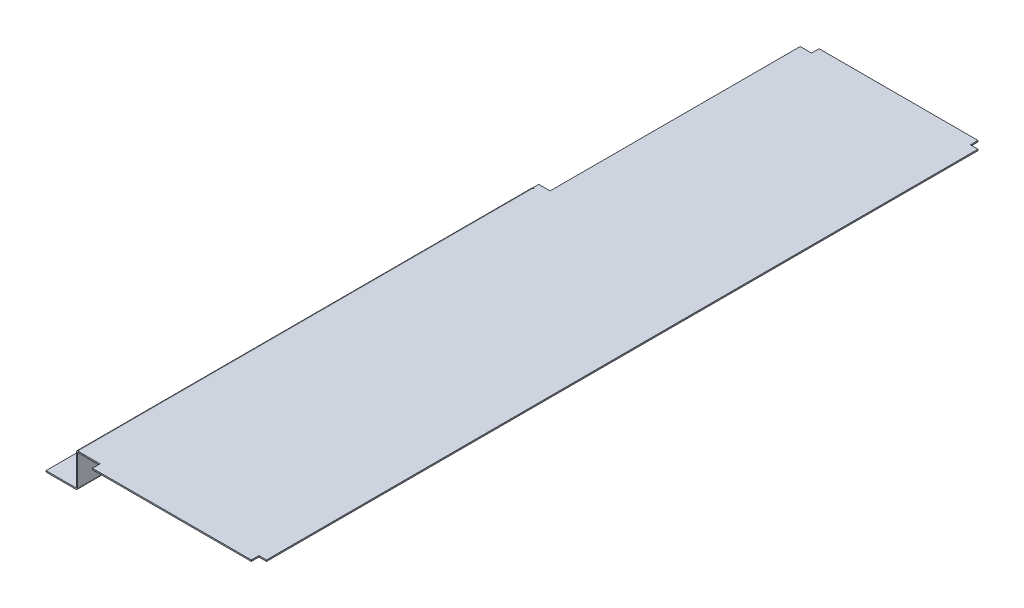
SolidWorks part; units mm, degrees
note: The reader was unsure of these and kept them because the rebuilt part matched: flange length of "Edge-Flange1", "Edge-Flange2".
ref_plane "Front Plane" through (0, 0, 0) normal (0, 0, 1) x (1, 0, 0)
ref_plane "Top Plane" through (0, 0, 0) normal (0, 1, 0) x (1, 0, 0)
ref_plane "Right Plane" through (0, 0, 0) normal (1, 0, 0) x (0, 0, -1)
sketch "Sketch1" plane through (0, 0, 0) normal (0, 1, 0) x (1, 0, 0)
  line L0 (-105.2709, 479.5) -> (-105.2709, 469.5)
  line L1 (-105.2709, -479.5) -> (104.4291, -479.5)
  line L2 (-120.2709, 139.5) -> (-120.2709, 469.5)
  line L3 (-105.2709, 479.5) -> (104.4291, 479.5)
  line L4 (114.4291, -469.5) -> (114.4291, 469.5)
  line L5 (0, 0) -> (114.9516, 469.5) construction
  line L6 (-114.9516, 469.5) -> (114.9516, -469.5) construction
  line L7 (-105.2709, 469.5) -> (-120.2709, 469.5)
  line L8 (104.4291, 479.5) -> (104.4291, 469.5)
  line L9 (104.4291, 469.5) -> (114.4291, 469.5)
  line L10 (114.4291, -469.5) -> (104.4291, -469.5)
  line L11 (104.4291, -469.5) -> (104.4291, -479.5)
  line L12 (-120.2709, -469.5) -> (-105.2709, -469.5)
  line L13 (-105.2709, -469.5) -> (-105.2709, -479.5)
  line L14 (-120.2709, -469.5) -> (-135.2709, -469.5)
  line L15 (-135.2709, -469.5) -> (-135.2709, 139.5)
  line L16 (-135.2709, 139.5) -> (-120.2709, 139.5)
  point P0 (0, 0)
  dimension "D2" = 609
  dimension "D3" = 15
  dimension "D4" = 10
  dimension "D5" = 10
  dimension "D6" = 10
  dimension "D7" = 10
  dimension "D8" = 10
  dimension "D9" = 15
  dimension "D10" = 10
  dimension "D11" = 15
  dimension "D12" = 234.7
base flange "Base-Flange1" sketch "Sketch1" thickness 1.7366 reverse thickness direction no parameters "D1"=0.7366
edge flange "Edge-Flange1" sketch "Sketch8" flange angle 90 flange length 43.7366 flange position material outside bend radius 0.7366 thickness 1.7366 relief rectangular parameters "D6"=10
sketch "Sketch8" plane through (-135.2709, -1.7366, 0) normal (-1, 0, 0) x (0, 0, -1)
  line L0 (139.5, 0) -> (-469.5, 0) construction
  line L1 (131, 0) -> (-469.1, 0)
  line L2 (-469.1, 0) -> (-469.1, 42)
  line L3 (-469.1, 42) -> (131, 42)
  line L4 (131, 42) -> (131, 0)
  dimension "D1" = 42
  dimension "D2" = 8.5
  dimension "D3" = 0.4
bend "EdgeBend1" bend radius 0.7366 bend angle 90 parameters "D5"=1
edge flange "Edge-Flange2" sketch "Sketch11" flange angle 90 flange length 41.7366 flange position material outside bend radius 0.7366 thickness 1.7366 relief rectangular parameters "D6"=10
sketch "Sketch11" plane through (-137.0075, -43.7366, 0) normal (0, -1, 0) x (0, 0, 1)
  line L0 (-131, 0) -> (469.1, 0) construction
  line L1 (-75.5, 0) -> (469.1, 0)
  line L2 (-75.5, 0) -> (-75.5, 40)
  line L3 (-75.5, 40) -> (469.1, 40)
  line L4 (469.1, 40) -> (469.1, 0)
  dimension "D1" = 55.5
  dimension "D2" = 40
bend "EdgeBend2" bend radius 0.7366 bend angle 90 parameters "D5"=2
sketch "Bend-Lines1" [suppressed] plane through (0, 0, 0) normal (0, 1, 0) x (1, 0, 0)
sketch "Bounding-Box1" [suppressed] plane through (0, 0, 0) normal (0, 1, 0) x (1, 0, 0)
sheet metal parameters "Sheet-Metal1" thickness 1.7366 parameters "D1"=0.7366
flat pattern "Flat-Pattern1" [suppressed]
sketch "Bend-Lines2" plane through (0, 0, 0) normal (0, 1, 0) x (1, 0, 0)
sketch3d "Bounding-Box2" [suppressed]
  line L0 (-135.2709, -479.5, 0) -> (-135.2709, 479.5, 0) construction
  line L1 (114.4291, -479.5, 0) -> (114.4291, 479.5, 0) construction
  line L2 (-135.2709, -479.5, 0) -> (114.4291, -479.5, 0) construction
  line L3 (-135.2709, 479.5, 0) -> (114.4291, 479.5, 0) construction
sheet metal parameters "Sheet-Metal2" thickness 1.7366 parameters "D1"=0.7366
flat pattern "Flat-Pattern1"
sketch "Bend-Lines2" plane through (0, 0, 0) normal (0, 1, 0) x (1, 0, 0)
  line L0 (-135.7948, 130.5) -> (-135.7948, -469.1) construction
  line L1 (-135.7948, 130.5) -> (-135.7948, -469.1) construction
sketch3d "Bounding-Box2" [suppressed]
  line L0 (-178.3187, -479.5, 0) -> (-178.3187, 479.5, 0) construction
  line L1 (114.4291, -479.5, 0) -> (114.4291, 479.5, 0) construction
  line L2 (-178.3187, -479.5, 0) -> (114.4291, -479.5, 0) construction
  line L3 (-178.3187, 479.5, 0) -> (114.4291, 479.5, 0) construction
bend of the flat pattern "Flatten-<EdgeBend1>1"
sheet metal parameters "Sheet-Metal3" thickness 1.7366 parameters "D1"=0.7366
flat pattern "Flat-Pattern1"
sketch "Bend-Lines2" plane through (0, 0, 0) normal (0, 1, 0) x (1, 0, 0)
  line L0 (-135.7948, 131) -> (-135.7948, -469.1) construction
  line L1 (-135.7948, 131) -> (-135.7948, -469.1) construction
  line L2 (-178.8426, 75.5) -> (-178.8426, -469.1) construction
  line L3 (-178.8426, 75.5) -> (-178.8426, -469.1) construction
sketch3d "Bounding-Box2" [suppressed]
  line L0 (-219.3665, -479.5, 0) -> (-219.3665, 479.5, 0) construction
  line L1 (114.4291, -479.5, 0) -> (114.4291, 479.5, 0) construction
  line L2 (-219.3665, -479.5, 0) -> (114.4291, -479.5, 0) construction
  line L3 (-219.3665, 479.5, 0) -> (114.4291, 479.5, 0) construction
bend of the flat pattern "Flatten-<EdgeBend1>1"
bend of the flat pattern "Flatten-<EdgeBend2>1"
